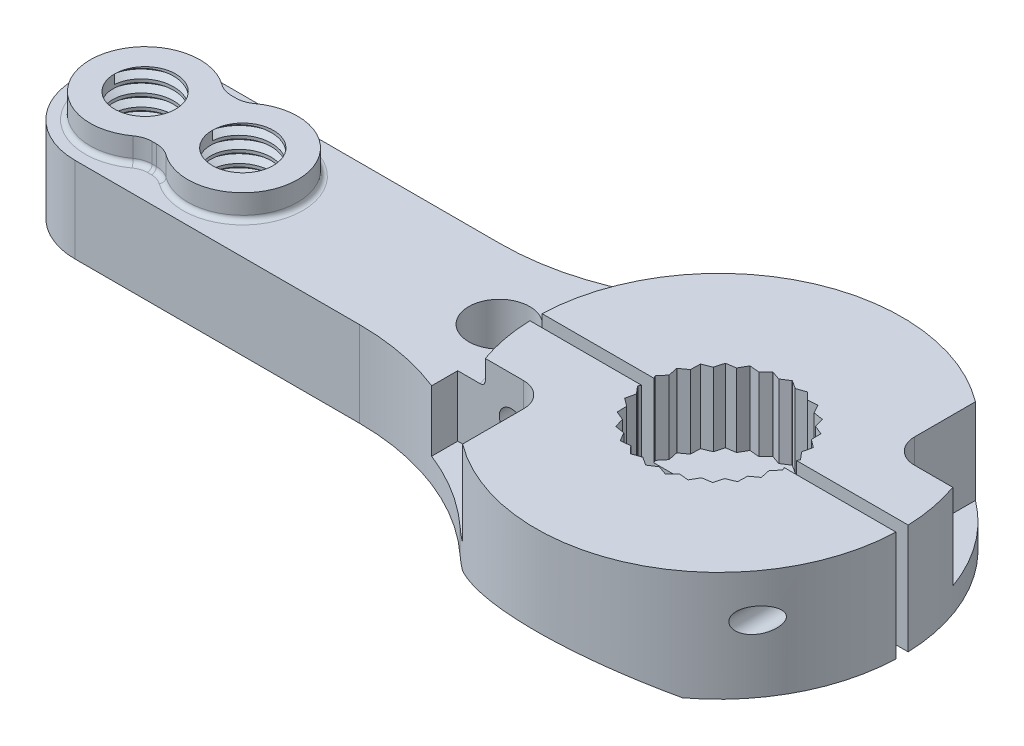
SolidWorks part; units mm, degrees
ref_plane "Front Plane" through (0, 0, 0) normal (0, 0, 1) x (1, 0, 0)
ref_plane "Top Plane" through (0, 0, 0) normal (0, 1, 0) x (1, 0, 0)
ref_plane "Right Plane" through (0, 0, 0) normal (1, 0, 0) x (0, 0, -1)
sketch "Sketch1" plane through (0, 0, 0) normal (0, 1, 0) x (1, 0, 0)
  line L0 (-23.5, 0) -> (0, 0) construction
  line L1 (-23.5, 2.875) -> (-11.8526, 2.875)
  line L2 (-23.5, 2.875) -> (0, 2.875) construction
  line L3 (-23.5, -2.875) -> (0, -2.875) construction
  line L4 (-23.5, -2.875) -> (-11.8526, -2.875)
  line L5 (-9, 0) -> (0, 0) construction
  line L6 (-9, 0.5) -> (0, 0.5) construction
  line L7 (-9, -0.5) -> (0, -0.5) construction
  arc A0 (-23.5, 2.875) -> (-23.5, -2.875) centre (-23.5, 0) ccw construction
  arc A1 (0, -2.875) -> (0, 2.875) centre (0, 0) ccw construction
  circle A2 centre (0, 0) radius 7.5 construction
  arc A3 (-23.5, 2.875) -> (-23.5, -2.875) centre (-23.5, 0) ccw
  arc A4 (-5.0797, 5.5179) -> (-5.0797, -5.5179) centre (0, 0) cw
  arc A5 (-11.8526, -2.875) -> (-5.0797, -5.5179) centre (-11.8526, -12.875) cw
  arc A6 (-5.0797, 5.5179) -> (-11.8526, 2.875) centre (-11.8526, 12.875) cw
  circle A7 centre (-9, 0) radius 1.5 construction
  arc A8 (-9, 0.5) -> (-9, -0.5) centre (-9, 0) ccw construction
  arc A9 (0, -0.5) -> (0, 0.5) centre (0, 0) ccw construction
  point P4 (-11.75, 0)
  point P18 (-6.9271, -2.875)
  point P21 (-6.9271, 2.875)
  point P24 (-4.5, 0)
  dimension "D3" = 16.5729
  dimension "D5" = 7.5
  dimension "D6" = 10
  dimension "D7" = 10
  dimension "D8" = 3
  dimension "D1" = 23.5
  dimension "D2" = 5.75
  dimension "D4" = 16.5729
  dimension "D9" = 1
extrude "Boss-Extrude1" add sketch "Sketch1" along normal blind 3.5
sketch "Sketch10" plane through (0, 3.5, 0) normal (0, 1, 0) x (1, 0, 0)
  circle A0 centre (0, 0) radius 7.5
extrude "Boss-Extrude3" add sketch "Sketch10" along normal blind 1
sketch "Sketch11" plane through (0, 3.5, 0) normal (0, 1, 0) x (1, 0, 0)
  line L5 (-23.5, 0) -> (-19.5, 0) construction
  line L6 (-21.5, -1.625) -> (-21.5, 1.625) construction
  line L7 (-2.475, 0) -> (2.475, 0) construction
  line L8 (-21.5838, -1.625) -> (-21.4162, -1.625)
  line L9 (-21.5838, 1.625) -> (-21.4162, 1.625)
  circle A0 centre (-23.5, 0) radius 2.25 construction
  circle A1 centre (-19.5, 0) radius 2.25 construction
  arc A2 (-22.1734, -1.8173) -> (-22.1734, 1.8173) centre (-23.5, 0) cw
  arc A3 (-20.8266, 1.8173) -> (-20.8266, -1.8173) centre (-19.5, 0) cw
  arc A4 (-22.1734, -1.8173) -> (-21.5838, -1.625) centre (-21.5838, -2.625) cw
  arc A5 (-20.8266, -1.8173) -> (-21.4162, -1.625) centre (-21.4162, -2.625) ccw
  arc A6 (-21.4162, 1.625) -> (-20.8266, 1.8173) centre (-21.4162, 2.625) ccw
  arc A7 (-21.5838, 1.625) -> (-22.1734, 1.8173) centre (-21.5838, 2.625) cw
  point P10 (-21.5023, 0)
  point P12 (-21.5, 0)
  point P19 (-21.9438, -1.625)
  point P23 (-21.0562, -1.625)
  point P26 (-21.0562, 1.625)
  point P29 (-21.9438, 1.625)
  dimension "D1" = 4.5
  dimension "D2" = 4.5
  dimension "D4" = 4
  dimension "D10" = 2.25
  dimension "D11" = 2.25
  dimension "D12" = 1
  dimension "D3" = 19.5
  dimension "D5" = 2.0023
  dimension "D6" = 4
  dimension "D7" = 0.8875
  dimension "D8" = 3.25
  dimension "D9" = 0.8875
extrude "Boss-Extrude4" add sketch "Sketch11" along normal blind 1
fillet "Fillet1" radius 0.2 8 edges at (-21.1061, 3.5, 1.6743) (-17.25, 3.5, 0) (-21.1061, 3.5, -1.6743) (-21.5, 3.5, -1.625) (-21.8939, 3.5, -1.6743) (-25.75, 3.5, 0) (-21.8939, 3.5, 1.6743) (-21.5, 3.5, 1.625)
fillet "Fillet2" radius 0.2 1 edges at (-7.5, 3.5, 0)
sketch "Sketch4" plane through (0, 0, 0) normal (0, -1, 0) x (1, 0, 0)
  circle A0 centre (0, 0) radius 5
extrude "Cut-Extrude1" cut sketch "Sketch4" against normal blind 1
sketch "Sketch7" plane through (0, 0, 0) normal (0, -1, 0) x (1, 0, 0)
  line L2 (9, -0.25) -> (-9, -0.25)
  line L3 (9, -0.25) -> (9, 0.25)
  line L4 (-9, -0.25) -> (-9, 0.25)
  line L5 (9, 0.25) -> (-9, 0.25)
  line L6 (9, -0.25) -> (-9, 0.25) construction
  line L7 (-9, -0.25) -> (9, 0.25) construction
  point P1 (0, 0)
  dimension "D1" = 0.25
  dimension "D2" = 9
extrude "Cut-Extrude4" cut sketch "Sketch7" against normal through all
hole_wizard "Tap Drill for M3x0.5 Tap3" positions "Sketch12" profile "Sketch13" hole size "M3x0.5" standard "ANSI Metric" end condition through all
sketch "Sketch12" plane through (0, 0, 0) normal (0, -1, 0) x (-1, 0, 0)
  line L0 (9, -0.25) -> (9, 0.25) construction
  point P0 (0, 0)
  point P3 (19.5, 0)
  point P5 (23.5, 0)
  point P7 (9, 0)
  dimension "D1" = 9
  dimension "D2" = 23.5
  dimension "D3" = 19.5
sketch "Sketch13" plane through (0, 0, 0) normal (1, 0, 0) x (0, 0, -1)
  line L0 (0, 0) -> (0, 4.5)
  line L1 (0, 4.5) -> (1.25, 4.5)
  line L2 (1.25, 4.5) -> (1.25, 0)
  line L5 (1.25, 0) -> (0, 0)
  line L11 (0, -6.35) -> (0, 107.95) construction
  dimension "Thru Hole Dia." = 2.5
  dimension "Thru Hole Depth" = 4.5
sketch "Sketch15" plane through (0, 0, 0) normal (0, 0, 1) x (1, 0, 0)
  line L3 (-6, 2.75) -> (0, 2.75) construction
  line L6 (0, -2.475) -> (0, 2.475) construction
  line L7 (0, 2.75) -> (6, 2.75) construction
  line L8 (8.25, 0) -> (-8.25, 0) construction
  circle A0 centre (-6, 2.75) radius 0.5
  circle A1 centre (6, 2.75) radius 0.5
  dimension "D1" = 1
  dimension "D2" = 1
  dimension "D3" = 6
  dimension "D4" = 2.75
  dimension "D5" = 2.75
extrude "Cut-Extrude5" cut sketch "Sketch15" against normal through all both and the other way through all
sketch "Sketch17" plane through (0, 4.5, 0) normal (0, 1, 0) x (1, 0, 0)
  line L0 (0, -2.475) -> (0, 2.475) construction
  line L1 (-2.475, 0) -> (2.475, 0) construction
  line L2 (0, 0) -> (-0.7258, -2.9109) construction
  line L3 (-0.7258, -2.9109) -> (0, 0)
  line L4 (0, -3) -> (0, 0) construction
  line L5 (-0.7258, -2.9109) -> (-0.3412, -2.7791)
  line L6 (-0.3412, -2.7791) -> (0, -3)
  line L7 (0, 0) -> (0, -3)
  circle A0 centre (0, 0) radius 3 construction
  dimension "D1" = 6
  dimension "D2" = 3
  dimension "D3" = 14
  dimension "D4" = 3
  dimension "D5" = 2.8
extrude "Cut-Extrude6" cut sketch "Sketch17" against normal blind 3
pattern_circular "CirPattern1" count 26 over 360 about axis through (0, 3.5, 0) along (0, -1, 0) of "Cut-Extrude6"
sketch "Sketch18" plane through (0, 0, 0) normal (1, 0, 0) x (0, 0, -1)
  line L0 (-6, 0) -> (-7.5, 0.866)
  line L2 (8.25, 0) -> (-8.25, 0) construction
  line L3 (-7.5, 0.866) -> (-7.5, 0)
  line L4 (-7.5, 0) -> (-6, 0)
  dimension "D1" = 30
  dimension "D2" = 1.5
  dimension "D3" = 6
extrude "Cut-Extrude7" cut sketch "Sketch18" against normal up to next and the other way up to next
mirror "Mirror1" about plane through (0, 0, 0) normal (0, 0, 1) of "Cut-Extrude7"
sketch "Sketch19" plane through (0, 0, 0) normal (0, 0, 1) x (1, 0, 0)
  line L0 (8.25, 0) -> (-8.25, 0) construction
  line L1 (-8.2, 4.5) -> (-4.5, 4.5)
  line L2 (-8.2, 4.5) -> (-8.2, 1)
  line L3 (-8.2, 1) -> (-4.5, 1)
  line L4 (-4.5, 4.5) -> (-4.5, 1)
  line L5 (7.4958, 4.5) -> (-7.4958, 4.5) construction
  line L6 (0, -2.475) -> (0, 2.475) construction
  point P0 (-6.4098, 2.75)
  dimension "D1" = 1
  dimension "D2" = 3.7
  dimension "D3" = 1.75
  dimension "D4" = 1.7902
  dimension "D5" = 4.5
extrude "Cut-Extrude8" cut sketch "Sketch19" along normal blind 9 from offset 2.5
fillet "Fillet6" radius 1 1 edges at (-4.5, 2.75, 2.5)
pattern_circular "CirPattern2" count 2 over 360 about axis through (0, 3.5, 0) along (0, -1, 0) of "Cut-Extrude8"
fillet "Fillet7" radius 1 1 edges at (4.5, 2.75, -2.5)
thread "Thread1" pitch 0.5 method cut profile "Thread Profile4" start angle 0, offset 0, length 0, pitch 0.5, diameter 2.5
ref_plane "Plane4" through (-24.75, 4.5, 0) normal (0, 0, 1) x (-1, 0, 0)
sketch "Thread Profile4" plane through (-24.75, 4.5, 0) normal (0, 0, 1) x (-1, 0, 0)
  line L0 (0, 0) -> (0, 0.5) construction
  line L1 (0, 0) -> (0.2706, 0.1562)
  line L2 (0.2706, 0.1562) -> (0.2706, 0.2187)
  line L3 (0.2706, 0.2187) -> (0, 0.375)
  line L4 (0.2706, 0.1875) -> (0, 0.1875) construction
  line L11 (0, 0) -> (0, 0.375)
  point P2 (0, 0)
  dimension "Pitch" = 0.5
  dimension "Profile_Angle" = 60
  dimension "Profile_Land" = 0.0625
  dimension "Profile_Height" = 0.2706
thread "Thread2" pitch 0.5 method cut profile "Thread Profile5" start angle 0, offset 0, length 0, pitch 0.5, diameter 2.5
ref_plane "Plane5" through (-20.75, 4.5, 0) normal (0, 0, 1) x (-1, 0, 0)
sketch "Thread Profile5" plane through (-20.75, 4.5, 0) normal (0, 0, 1) x (-1, 0, 0)
  line L0 (0, 0) -> (0, 0.5) construction
  line L1 (0, 0) -> (0.2706, 0.1562)
  line L2 (0.2706, 0.1562) -> (0.2706, 0.2187)
  line L3 (0.2706, 0.2187) -> (0, 0.375)
  line L4 (0.2706, 0.1875) -> (0, 0.1875) construction
  line L11 (0, 0) -> (0, 0.375)
  point P2 (0, 0)
  dimension "Pitch" = 0.5
  dimension "Profile_Angle" = 60
  dimension "Profile_Land" = 0.0625
  dimension "Profile_Height" = 0.2706
